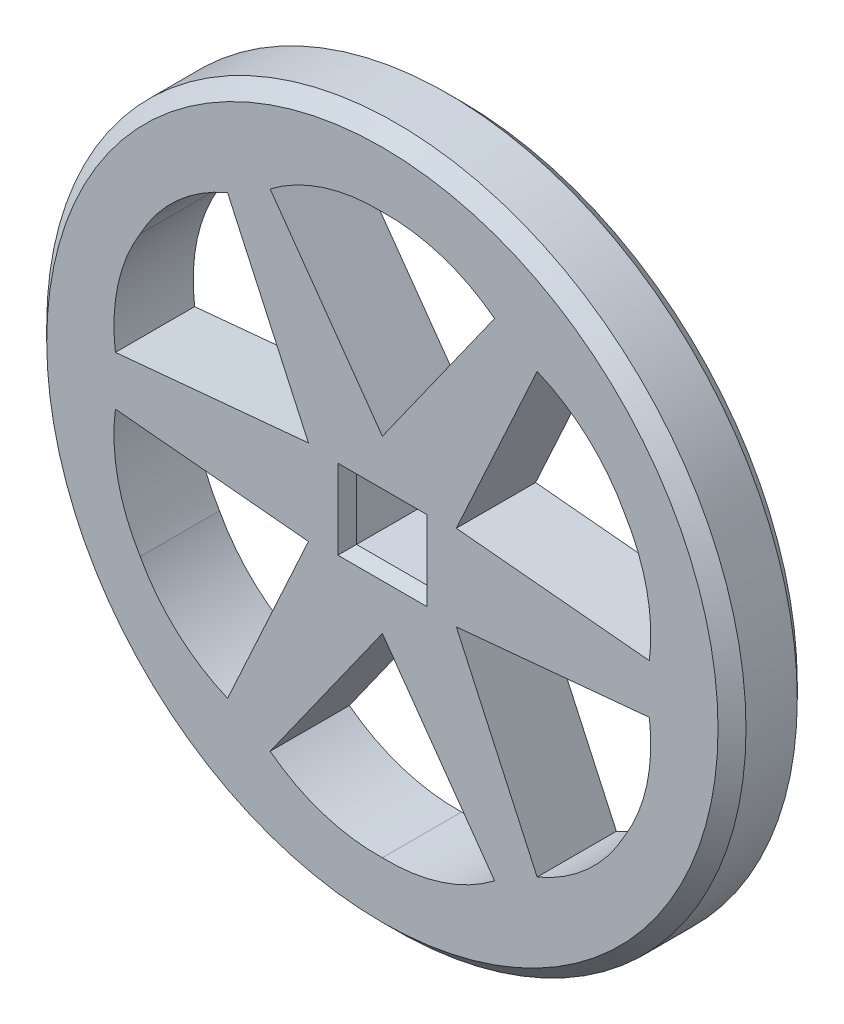
SolidWorks part; units mm, degrees
ref_plane "Front Plane" through (0, 0, 0) normal (0, 0, 1) x (1, 0, 0)
ref_plane "Top Plane" through (0, 0, 0) normal (0, 1, 0) x (1, 0, 0)
ref_plane "Right Plane" through (0, 0, 0) normal (1, 0, 0) x (0, 0, -1)
sketch "Sketch1" plane through (0, 0, 0) normal (0, 0, 1) x (1, 0, 0)
  line L1 (4.275, -3.775) -> (-4.275, -3.775)
  line L2 (4.275, -3.775) -> (4.275, 3.775)
  line L3 (4.275, 3.775) -> (-4.275, 3.775)
  line L4 (-4.275, -3.775) -> (-4.275, 3.775)
  circle A0 centre (0, 0) radius 37.5
  point P3 (0, 3.775)
  point P9 (4.275, 0)
  dimension "D1" = 75
  dimension "D2" = 8.55
  dimension "D3" = 7.55
extrude "Boss-Extrude1" add sketch "Sketch1" along normal mid plane 8.5
sketch "Sketch2" plane through (0, 0, 0) normal (0, 0, 1) x (1, 0, 0)
  line L0 (0, 0) -> (0, 32.5712) construction
  line L1 (0, 9.1586) -> (-12.0371, 26.1152)
  line L2 (0, 9.1586) -> (12.0371, 26.1152)
  arc A0 (-12.0371, 26.1152) -> (0, 29.9881) centre (-0.5568, 11.0765) cw
  arc A1 (12.0371, 26.1152) -> (0, 29.9881) centre (0.5568, 11.0765) ccw
extrude "Cut-Extrude1" cut sketch "Sketch2" along normal through all both and the other way through all
pattern_circular "CirPattern1" count 6 over 360 about axis through (0, 0, 4.25) along (0, 0, -1) of "Cut-Extrude1" reverse direction yes
sketch "Sketch3" plane through (0, 0, 0) normal (0, 0, 1) x (1, 0, 0)
  circle A0 centre (0, 0) radius 37.5
  circle A1 centre (0, 0) radius 37.2
  circle A2 centre (0, 0) radius 37.5 construction
  dimension "D1" = 0.3
chamfer "Chamfer1" distance 0.5 distance2 1.5 4 edges at (4.275, 0, 4.25) (0, 3.775, 4.25) (-4.275, 0, 4.25) (0, -3.775, 4.25) first distance on face at (37.5, 0, 4.25)
chamfer "Chamfer2" distance 1.5 angle 45 2 edges at (37.5, 0, 4.25) (37.5, 0, -4.25)
